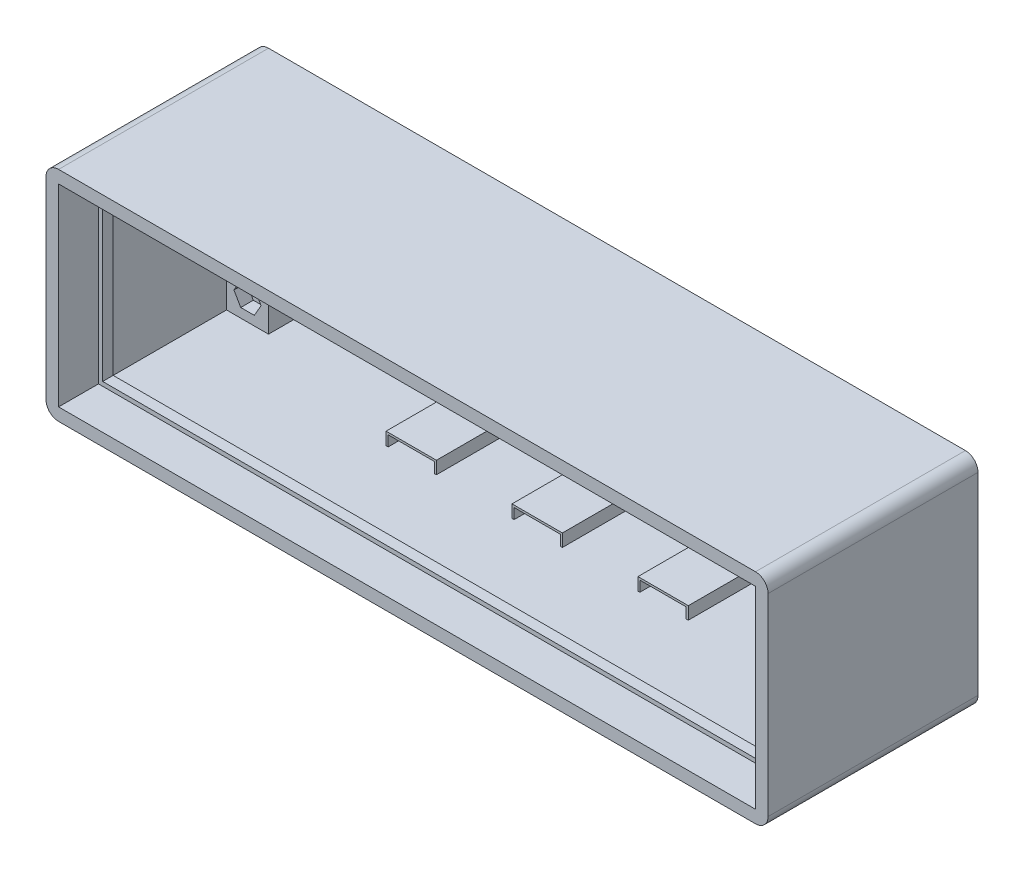
SolidWorks part; units mm, degrees
note: The reader was unsure of these and kept them because the rebuilt part matched: shared geometry of "草图1<11>", "草图1<12>", "草图1<16>", "草图1<17>", "草图1<18>", "草图1<19>", "草图1<20>", "草图1<21>", "草图1<22>", "草图1<23>", "草图1<24>", "草图1<25>", "草图1<26>", "草图1<27>".
ref_plane "前视基准面" through (0, 0, 0) normal (0, 0, 1) x (1, 0, 0)
ref_plane "上视基准面" through (0, 0, 0) normal (0, 1, 0) x (1, 0, 0)
ref_plane "右视基准面" through (0, 0, 0) normal (1, 0, 0) x (0, 0, -1)
sketch "草图1" plane through (0, 0, 0) normal (0, 0, 1) x (1, 0, 0)
  line L1 (-39.3421, 27.9845) -> (126.6579, 27.9845)
  line L2 (-39.3421, 27.9845) -> (-39.3421, -18.0155)
  line L3 (-39.3421, -18.0155) -> (126.6579, -18.0155)
  line L4 (126.6579, 27.9845) -> (126.6579, -18.0155)
  line L5 (-42.3421, 30.9845) -> (129.6579, 30.9845)
  line L6 (-42.3421, 30.9845) -> (-42.3421, -21.0155)
  line L7 (-42.3421, -21.0155) -> (129.6579, -21.0155)
  line L8 (129.6579, 30.9845) -> (129.6579, -21.0155)
  line L9 (-38.3421, 26.9845) -> (125.6579, 26.9845)
  line L10 (-38.3421, 26.9845) -> (-38.3421, -17.0155)
  line L11 (-38.3421, -17.0155) -> (125.6579, -17.0155)
  line L12 (125.6579, 26.9845) -> (125.6579, -17.0155)
  line L13 (-38.3421, 26.9845) -> (-26.7868, 26.9845)
  line L14 (-38.3421, 26.9845) -> (-38.3421, 16.2567)
  line L15 (-39.3421, 27.9845) -> (-29.3421, 27.9845)
  line L16 (-39.3421, 27.9845) -> (-39.3421, 17.9845)
  line L17 (-39.3421, 17.9845) -> (-32.3421, 17.9845)
  line L18 (-29.3421, 27.9845) -> (-29.3421, 20.9845)
  line L19 (126.6579, 27.9845) -> (116.6579, 27.9845)
  line L20 (126.6579, 27.9845) -> (126.6579, 17.9845)
  line L21 (126.6579, 17.9845) -> (119.6579, 17.9845)
  line L22 (116.6579, 27.9845) -> (116.6579, 20.9845)
  line L23 (126.6579, -18.0155) -> (116.6579, -18.0155)
  line L24 (126.6579, -18.0155) -> (126.6579, -8.0155)
  line L25 (126.6579, -8.0155) -> (119.6579, -8.0155)
  line L26 (116.6579, -18.0155) -> (116.6579, -11.0155)
  line L27 (-39.3421, -18.0155) -> (-29.3421, -18.0155)
  line L28 (-39.3421, -18.0155) -> (-39.3421, -8.0155)
  line L29 (-39.3421, -8.0155) -> (-32.3421, -8.0155)
  line L30 (-29.3421, -18.0155) -> (-29.3421, -11.0155)
  line L31 (-31.109, 22.9845) -> (-32.7255, 25.7845)
  line L32 (-32.7255, 25.7845) -> (-35.9587, 25.7845)
  line L33 (-35.9587, 25.7845) -> (-37.5753, 22.9845)
  line L34 (-37.5753, 22.9845) -> (-35.9587, 20.1845)
  line L35 (-35.9587, 20.1845) -> (-32.7255, 20.1845)
  line L36 (-32.7255, 20.1845) -> (-31.109, 22.9845)
  line L37 (118.4247, 22.9845) -> (120.0413, 20.1845)
  line L38 (120.0413, 20.1845) -> (123.2745, 20.1845)
  line L39 (123.2745, 20.1845) -> (124.891, 22.9845)
  line L40 (124.891, 22.9845) -> (123.2745, 25.7845)
  line L41 (123.2745, 25.7845) -> (120.0413, 25.7845)
  line L42 (120.0413, 25.7845) -> (118.4247, 22.9845)
  line L43 (124.891, -13.0155) -> (123.2745, -10.2155)
  line L44 (123.2745, -10.2155) -> (120.0413, -10.2155)
  line L45 (120.0413, -10.2155) -> (118.4247, -13.0155)
  line L46 (118.4247, -13.0155) -> (120.0413, -15.8155)
  line L47 (120.0413, -15.8155) -> (123.2745, -15.8155)
  line L48 (123.2745, -15.8155) -> (124.891, -13.0155)
  line L49 (-31.109, -13.0155) -> (-32.7255, -10.2155)
  line L50 (-32.7255, -10.2155) -> (-35.9587, -10.2155)
  line L51 (-35.9587, -10.2155) -> (-37.5753, -13.0155)
  line L52 (-37.5753, -13.0155) -> (-35.9587, -15.8155)
  line L53 (-35.9587, -15.8155) -> (-32.7255, -15.8155)
  line L54 (-32.7255, -15.8155) -> (-31.109, -13.0155)
  arc A0 (-32.3421, 17.9845) -> (-29.3421, 20.9845) centre (-32.3421, 20.9845) ccw
  arc A1 (119.6579, 17.9845) -> (116.6579, 20.9845) centre (119.6579, 20.9845) cw
  arc A2 (119.6579, -8.0155) -> (116.6579, -11.0155) centre (119.6579, -11.0155) ccw
  arc A3 (-32.3421, -8.0155) -> (-29.3421, -11.0155) centre (-32.3421, -11.0155) cw
  circle A4 centre (-34.3421, 22.9845) radius 2.8 construction
  circle A5 centre (121.6579, 22.9845) radius 2.8 construction
  circle A6 centre (121.6579, -13.0155) radius 2.8 construction
  circle A7 centre (-34.3421, -13.0155) radius 2.8 construction
  circle A8 centre (121.6579, 22.9845) radius 1.6
  circle A9 centre (121.6579, -13.0155) radius 1.6
  circle A10 centre (-34.3421, -13.0155) radius 1.6
  circle A11 centre (-34.3421, 22.9845) radius 1.6
  point P19 (-29.3421, 17.9845)
  point P25 (116.6579, 17.9845)
  point P31 (116.6579, -8.0155)
  point P37 (-29.3421, -8.0155)
  dimension "D13" = 3
  dimension "D16" = 3
  dimension "D19" = 3
  dimension "D22" = 3
  dimension "D32" = 5
  dimension "D1" = 166
  dimension "D2" = 46
  dimension "D3" = 52
  dimension "D4" = 172
  dimension "D5" = 3
  dimension "D6" = 3
  dimension "D7" = 44
  dimension "D8" = 164
  dimension "D9" = 1
  dimension "D10" = 5
  dimension "D11" = 10
  dimension "D12" = 10
  dimension "D14" = 10
  dimension "D15" = 10
  dimension "D17" = 10
  dimension "D18" = 10
  dimension "D20" = 10
  dimension "D21" = 10
  dimension "D23" = 5
  dimension "D26" = 5
  dimension "D27" = 5
  dimension "D30" = 5
  dimension "D31" = 5
  dimension "D34" = 5
extrude "凸台-拉伸1" add sketch "草图1" along normal blind 50 contours L8 L5 L6 L7 L1 L4 L3 L2
fillet "圆角1" radius 3 4 edges at (129.6579, -21.0155, 25) (129.6579, 30.9845, 25) (-42.3421, -21.0155, 25) (-42.3421, 30.9845, 25)
extrude "凸台-拉伸3" add sketch "草图1<11>" against normal blind 12 from surface at 50 contours L25 L4 L21 L12 | L1 L22 L9 L12 L21 L4 | L26 L3 L4 L25 L12 L11 | L30 L3 L26 L11 | L22 L1 L18 L13 L9 | L18 L1 L2 L17 L10 L9 | L2 L29 L10 L14 L17 | L3 L30 L11 L10 L29 L2 starting at face at (43.6579, 4.9845, 50)
sketch "草图1<11>" plane through (0, 0, 0) normal (0, 0, 1) x (1, 0, 0) same geometry as "草图1"
extrude "切除-拉伸1" cut sketch "草图1<12>" against normal blind 9.5 from surface at 50 contours L18 L1 L2 L17 L10 L9 | L22 L1 L18 L13 L9 | L2 L29 L10 L14 L17 | L3 L30 L11 L10 L29 L2 | L30 L3 L26 L11 | L25 L4 L21 L12 | L1 L22 L9 L12 L21 L4 | L26 L3 L4 L25 L12 L11 starting at face at (43.6579, 4.9845, 50)
sketch "草图1<12>" plane through (0, 0, 0) normal (0, 0, 1) x (1, 0, 0) same geometry as "草图1"
extrude "凸台-拉伸5" add sketch "草图1<16>" along normal blind 10 contours L18 L1 L2 L17 L10 L9 | L17 A0 L18 L9 L10 L36 L35 L34 L33 L32 L31 | L35 L36 L31 L32 L33 L34 A11
sketch "草图1<16>" plane through (0, 0, 0) normal (0, 0, 1) x (1, 0, 0) same geometry as "草图1"
extrude "凸台-拉伸6" add sketch "草图1<17>" along normal blind 10 contours L1 L22 L9 L12 L21 L4 | A1 L21 L12 L9 L22 L42 L41 L40 L39 L38 L37 | L41 L42 L37 L38 L39 L40 A8
sketch "草图1<17>" plane through (0, 0, 0) normal (0, 0, 1) x (1, 0, 0) same geometry as "草图1"
extrude "凸台-拉伸7" add sketch "草图1<18>" along normal blind 10 contours L3 L30 L11 L10 L29 L2 | A3 L29 L10 L11 L30 L54 L53 L52 L51 L50 L49 | L53 L54 L49 L50 L51 L52 A10
sketch "草图1<18>" plane through (0, 0, 0) normal (0, 0, 1) x (1, 0, 0) same geometry as "草图1"
extrude "凸台-拉伸8" add sketch "草图1<19>" along normal blind 10 contours L26 L3 L4 L25 L12 L11 | L25 A2 L26 L11 L12 L48 L47 L46 L45 L44 L43 | L47 L48 L43 L44 L45 L46 A9
sketch "草图1<19>" plane through (0, 0, 0) normal (0, 0, 1) x (1, 0, 0) same geometry as "草图1"
extrude "切除-拉伸2" cut sketch "草图1<20>" against normal blind 3 from surface at 10 contours L32 L33 L34 L35 L36 L31 starting at face at (-33.8179, 22.4603, 10)
sketch "草图1<20>" plane through (0, 0, 0) normal (0, 0, 1) x (1, 0, 0) same geometry as "草图1"
extrude "切除-拉伸3" cut sketch "草图1<21>" against normal blind 3 from surface at 10 contours L50 L51 L52 L53 L54 L49 starting at face at (-33.8179, -12.4912, 10)
sketch "草图1<21>" plane through (0, 0, 0) normal (0, 0, 1) x (1, 0, 0) same geometry as "草图1"
extrude "切除-拉伸5" cut sketch "草图1<22>" against normal blind 3 from surface at 10 contours L48 L43 L44 L45 L46 L47 starting at face at (121.1336, -12.4912, 10)
sketch "草图1<22>" plane through (0, 0, 0) normal (0, 0, 1) x (1, 0, 0) same geometry as "草图1"
extrude "切除-拉伸6" cut sketch "草图1<23>" against normal blind 3 from surface at 10 contours L38 L39 L40 L41 L42 L37 starting at face at (121.1336, 22.4603, 10)
sketch "草图1<23>" plane through (0, 0, 0) normal (0, 0, 1) x (1, 0, 0) same geometry as "草图1"
extrude "切除-拉伸8" cut sketch "草图1<24>" along normal blind 3 contours L18 L1 L2 L17 L10 L9 | L17 A0 L18 L9 L10 L36 L35 L34 L33 L32 L31 | L35 L36 L31 L32 L33 L34 A11
sketch "草图1<24>" plane through (0, 0, 0) normal (0, 0, 1) x (1, 0, 0) same geometry as "草图1"
extrude "切除-拉伸9" cut sketch "草图1<25>" along normal blind 3 contours A3 L29 L10 L11 L30 L54 L53 L52 L51 L50 L49 | L3 L30 L11 L10 L29 L2 | L53 L54 L49 L50 L51 L52 A10
sketch "草图1<25>" plane through (0, 0, 0) normal (0, 0, 1) x (1, 0, 0) same geometry as "草图1"
extrude "切除-拉伸10" cut sketch "草图1<26>" along normal blind 3 contours A1 L21 L12 L9 L22 L42 L41 L40 L39 L38 L37 | L1 L22 L9 L12 L21 L4 | L41 L42 L37 L38 L39 L40 A8
sketch "草图1<26>" plane through (0, 0, 0) normal (0, 0, 1) x (1, 0, 0) same geometry as "草图1"
extrude "切除-拉伸11" cut sketch "草图1<27>" along normal blind 3 contours L25 A2 L26 L11 L12 L48 L47 L46 L45 L44 L43 | L47 L48 L43 L44 L45 L46 A9 | L26 L3 L4 L25 L12 L11
sketch "草图1<27>" plane through (0, 0, 0) normal (0, 0, 1) x (1, 0, 0) same geometry as "草图1"
sketch "草图3" plane through (0, -21.0155, 0) normal (0, -1, 0) x (1, 0, 0)
  line L0 (-39.3421, 0) -> (126.6579, 0) construction
  line L1 (79.6579, 3) -> (67.6579, 3)
  line L2 (79.6579, 3) -> (79.6579, 19)
  line L3 (79.6579, 19) -> (67.6579, 19)
  line L4 (67.6579, 3) -> (67.6579, 19)
  line L5 (49.6579, 3) -> (37.6579, 3)
  line L6 (49.6579, 3) -> (49.6579, 19)
  line L7 (49.6579, 19) -> (37.6579, 19)
  line L8 (37.6579, 3) -> (37.6579, 19)
  line L9 (19.6579, 3) -> (7.6579, 3)
  line L10 (19.6579, 3) -> (19.6579, 19)
  line L11 (19.6579, 19) -> (7.6579, 19)
  line L12 (7.6579, 3) -> (7.6579, 19)
  line L13 (129.6579, 50) -> (129.6579, 0) construction
  line L14 (-42.3421, 0) -> (-42.3421, 50) construction
  dimension "D1" = 16
  dimension "D2" = 12
  dimension "D3" = 3
  dimension "D5" = 50
  dimension "D6" = 50
  dimension "D4" = 3
extrude "凸台-拉伸12" add sketch "草图3" against normal blind 6
sketch3d "3D草图3"
  line L6 (79.1225, -15.5155, 3) -> (68.1225, -15.5155, 3)
  line L7 (79.1225, -15.5155, 3) -> (79.1225, -18.0155, 3)
  line L8 (79.1225, -18.0155, 3) -> (68.1225, -18.0155, 3)
  line L9 (68.1225, -15.5155, 3) -> (68.1225, -18.0155, 3)
  dimension "D1" = 11
  dimension "D2" = 2.5
extrude "切除-拉伸13" cut sketch "3D草图3" along direction (0, 0, -1) on the side against the normal up to next (16 mm away)
sketch "草图4" plane through (0, 0, 3) normal (0, 0, -1) x (-1, 0, 0)
  line L0 (-49.6579, -18.0155) -> (-37.6579, -18.0155) construction
  line L1 (-49.1579, -15.5155) -> (-38.1579, -15.5155)
  line L2 (-49.1579, -15.5155) -> (-49.1579, -18.0155)
  line L3 (-49.1579, -18.0155) -> (-38.1579, -18.0155)
  line L4 (-38.1579, -15.5155) -> (-38.1579, -18.0155)
  line L5 (-49.6579, -15.0155) -> (-49.6579, -18.0155) construction
  line L6 (-19.6579, -18.0155) -> (-7.6579, -18.0155) construction
  line L7 (-19.1579, -15.5155) -> (-8.1579, -15.5155)
  line L8 (-19.1579, -15.5155) -> (-19.1579, -18.0155)
  line L9 (-19.1579, -18.0155) -> (-8.1579, -18.0155)
  line L10 (-8.1579, -15.5155) -> (-8.1579, -18.0155)
  line L11 (-19.6579, -15.0155) -> (-19.6579, -18.0155) construction
  dimension "D1" = 11
  dimension "D2" = 2.5
  dimension "D3" = 0.5
  dimension "D4" = 11
  dimension "D5" = 2.5
  dimension "D6" = 0.5
extrude "切除-拉伸14" cut sketch "草图4" against normal up to next
sketch3d "3D草图5"
  circle A0 centre (73.6383, -21.0155, 13.0097) radius 6
  circle A1 centre (43.6233, -21.0155, 13.0005) radius 6
  circle A2 centre (13.6762, -21.0155, 12.9804) radius 6
  point P5 (73.6383, -27.0155, 13.0097)
  point P6 (43.6233, -27.0155, 13.0005)
  point P9 (13.6762, -27.0155, 12.9804)
extrude "切除-拉伸16" cut sketch "3D草图5" along direction (0, 1, 0) on the side of the normal blind 0.5 from surface at 0
chamfer "倒角2" distance 0.5 angle 45 3 edges
